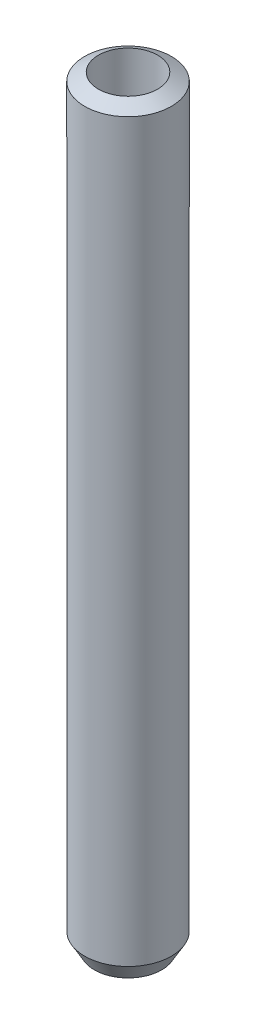
SolidWorks part; units mm, degrees
ref_plane "Front Plane" through (0, 0, 0) normal (0, 0, 1) x (1, 0, 0)
ref_plane "Top Plane" through (0, 0, 0) normal (0, 1, 0) x (1, 0, 0)
ref_plane "Right Plane" through (0, 0, 0) normal (1, 0, 0) x (0, 0, -1)
sketch "Sketch1" plane through (0, 0, 0) normal (0, 1, 0) x (1, 0, 0)
  circle A0 centre (0, 0) radius 22.5
  dimension "SHAFT_OD" = 45
extrude "Boss-Extrude1" add sketch "Sketch1" along normal blind 395.8121
sketch "Sketch2" plane through (0, 0, 0) normal (0, 1, 0) x (1, 0, 0)
  circle A0 centre (0, 0) radius 15.3464
  dimension "BORE_D" = 30.6929
extrude "Cut-Extrude1" cut sketch "Sketch2" along normal through all
chamfer "Chamfer1" distance 5.029 angle 60 2 edges at (0, 395.8121, 22.5) (0, 0, 22.5) first distance on face at (0, 395.8121, 22.5) first distance on face at (0, 0, 15.3464)
